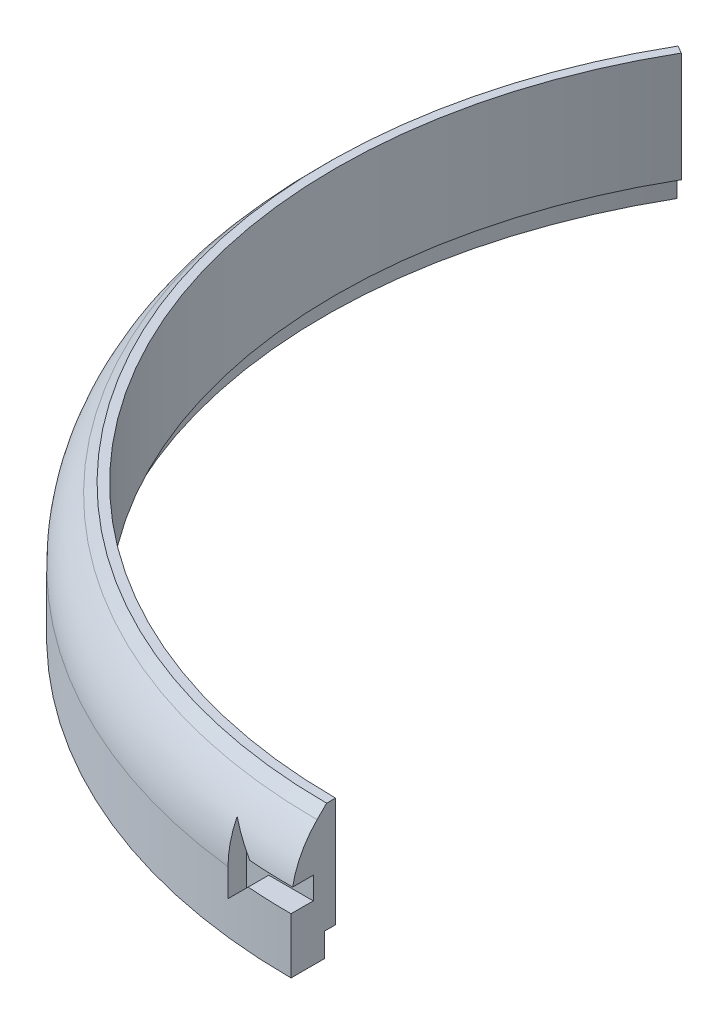
SolidWorks part; units mm, degrees
ref_plane "Front Plane" through (0, 0, 0) normal (0, 0, 1) x (1, 0, 0)
ref_plane "Top Plane" through (0, 0, 0) normal (0, 1, 0) x (1, 0, 0)
ref_plane "Right Plane" through (0, 0, 0) normal (1, 0, 0) x (0, 0, -1)
sketch "Sketch1" plane through (0, 0, 0) normal (0, 1, 0) x (1, 0, 0)
  line L0 (-114.7484, 66.25) -> (-106.0881, 61.25)
  line L1 (0, -132.5) -> (0, -122.5)
  arc A0 (-106.0881, 61.25) -> (0, -122.5) centre (0, 0) ccw
  arc A2 (-114.7484, 66.25) -> (0, -132.5) centre (0, 0) ccw
  circle A3 centre (0, 0) radius 132.5 construction
  circle A4 centre (0, 0) radius 122.5 construction
  dimension "D1" = 245
  dimension "D2" = 10
  dimension "D3" = 120
extrude "Boss-Extrude1" add sketch "Sketch1" along normal blind 30 contours A0 L1 A2 L0
sketch "Sketch2" plane through (0, 0, 0) normal (0, 1, 0) x (1, 0, 0)
  circle A0 centre (0, 0) radius 125
  dimension "D1" = 250
extrude "Cut-Extrude1" cut sketch "Sketch2" along normal blind 5.35
chamfer "Chamfer1" [suppressed] distance 1 angle 45
ref_plane "Plane1" through (0, 0, 132.5) normal (0, 0, 1) x (1, 0, 0)
sketch "Sketch3" plane through (0, 0, 132.5) normal (0, 0, 1) x (1, 0, 0)
  line L0 (0, 30) -> (0, 45.5478) construction
  line L1 (0, 30) -> (0, 0) construction
  line L2 (0, 17.5) -> (-10, 17.5)
  line L3 (0, 17.5) -> (0, 12.5)
  line L4 (0, 12.5) -> (-10, 12.5)
  line L5 (-10, 17.5) -> (-10, 12.5)
  line L6 (-10, 17.5) -> (-15, 22.5)
  line L7 (-15, 22.5) -> (-15, 7.5)
  line L8 (-15, 7.5) -> (-10, 12.5)
  line L9 (0, 15) -> (-10, 15) construction
  point P14 (-15, 15)
  dimension "D1" = 5
  dimension "D2" = 135
  dimension "D3" = 5
  dimension "D4" = 10
extrude "Cut-Extrude2" cut sketch "Sketch3" against normal blind 5 contours L2 L5 L4 L3 | L7 L8 L5 L6 region at (-5, 15, 132.5) region at (-12.9167, 15, 132.5)
ref_plane "Plane2" through (0, 0, 0) normal (0.5, 0, 0.866) x (0.866, 0, -0.5)
mirror "Mirror1" about plane through (0, 0, 0) normal (0.5, 0, 0.866) of "Cut-Extrude2"
chamfer "Chamfer2" distance 8 angle 45 1 edges at (-114.7484, 30, 66.25)
fillet "Fillet1" radius 20 1 edges at (-114.7484, 22, 66.25)
